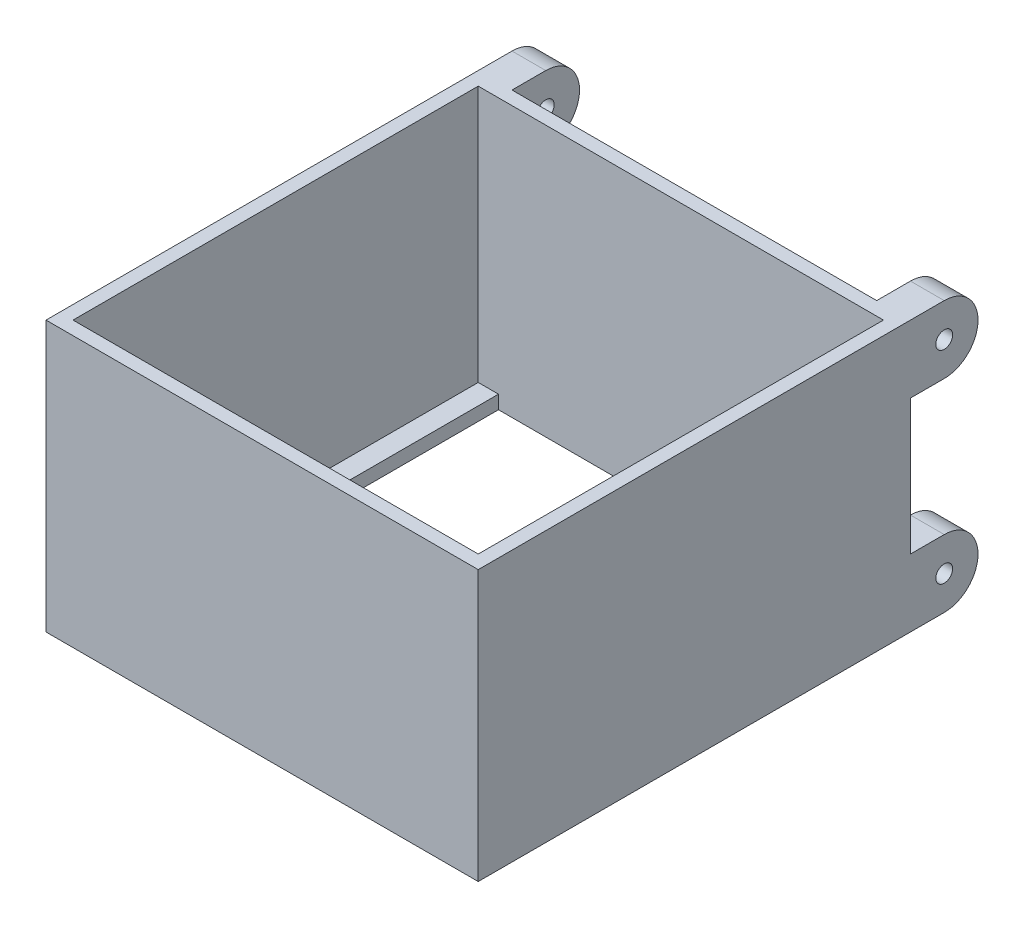
SolidWorks part; units mm, degrees
ref_plane "Front Plane" through (0, 0, 0) normal (0, 0, 1) x (1, 0, 0)
ref_plane "Top Plane" through (0, 0, 0) normal (0, 1, 0) x (1, 0, 0)
ref_plane "Right Plane" through (0, 0, 0) normal (1, 0, 0) x (0, 0, -1)
sketch "Sketch1" plane through (0, 0, 0) normal (0, 1, 0) x (1, 0, 0)
  line L0 (-40.64, 40.64) -> (40.64, 40.64)
  line L1 (-38.1, 38.1) -> (38.1, 38.1)
  line L2 (-38.1, 38.1) -> (-38.1, -38.1)
  line L3 (-38.1, -38.1) -> (38.1, -38.1)
  line L4 (38.1, 38.1) -> (38.1, -38.1)
  line L5 (40.64, 40.64) -> (40.64, -40.64)
  line L6 (-40.64, -40.64) -> (40.64, -40.64)
  line L7 (-40.64, 40.64) -> (-40.64, -40.64)
  point P4 (0, 38.1)
  point P6 (-38.1, 0)
  dimension "D1" = 76.2
  dimension "D2" = 76.2
  dimension "D3" = 2.54
extrude "Boss-Extrude1" add sketch "Sketch1" along normal blind 50.8
sketch "Sketch2" plane through (0, 0, 0) normal (0, 1, 0) x (1, 0, 0)
  line L0 (-38.1, -38.1) -> (38.1, -38.1) construction
  line L1 (-38.1, 38.1) -> (-34.29, 38.1)
  line L2 (-38.1, 38.1) -> (-38.1, -38.1)
  line L3 (-38.1, -38.1) -> (-34.29, -38.1)
  line L4 (-34.29, 38.1) -> (-34.29, -38.1)
  line L5 (0, 38.1) -> (0, -38.1) construction
  line L6 (38.1, 38.1) -> (-38.1, 38.1) construction
  line L7 (38.1, -38.1) -> (34.29, -38.1)
  line L8 (34.29, 38.1) -> (34.29, -38.1)
  line L9 (38.1, 38.1) -> (34.29, 38.1)
  line L10 (38.1, 38.1) -> (38.1, -38.1)
  dimension "D1" = 3.81
extrude "Boss-Extrude2" add sketch "Sketch2" along normal blind 2.54
fillet "Fillet1" [suppressed] radius 1.27
ref_plane "Plane1" through (0, 0, 0) normal (-1, 0, 0) x (0, 0, 1)
ref_plane "Plane2" through (0, 0, 0) normal (0, 0, 1) x (1, 0, 0)
ref_plane "Plane3" through (0, 25.4, 0) normal (0, -1, 0) x (-1, 0, 0)
sketch "Sketch3" plane through (40.64, 0, 0) normal (1, 0, 0) x (0, 0, -1)
  line L0 (46.99, 4.7752) -> (46.99, 0) construction
  line L1 (46.99, 12.7) -> (40.64, 12.7)
  line L2 (46.99, 12.7) -> (46.99, 7.9248) construction
  line L3 (46.99, 0) -> (40.64, 0)
  line L4 (40.64, 12.7) -> (40.64, 0)
  circle A0 centre (46.99, 6.35) radius 1.5748
  arc A1 (46.99, 0) -> (46.99, 12.7) centre (46.99, 6.35) ccw
  dimension "D1" = 3.1496
  dimension "D2" = 12.7
extrude "Boss-Extrude3" add sketch "Sketch3" against normal blind 6.35
sketch "Sketch4" plane through (40.64, 0, 0) normal (1, 0, 0) x (0, 0, -1)
  line L0 (46.99, 42.8625) -> (46.99, 38.1) construction
  line L1 (46.99, 50.8) -> (40.64, 50.8)
  line L2 (46.99, 50.8) -> (46.99, 46.0375) construction
  line L3 (46.99, 38.1) -> (40.64, 38.1)
  line L4 (40.64, 50.8) -> (40.64, 38.1)
  circle A0 centre (46.99, 44.45) radius 1.5875
  arc A1 (46.99, 38.1) -> (46.99, 50.8) centre (46.99, 44.45) ccw
  dimension "D1" = 3.175
  dimension "D2" = 6.35
extrude "Boss-Extrude4" add sketch "Sketch4" against normal blind 6.35
mirror "Mirror1" about plane through (0, 0, 0) normal (-1, 0, 0) of "Boss-Extrude4", "Boss-Extrude3"
